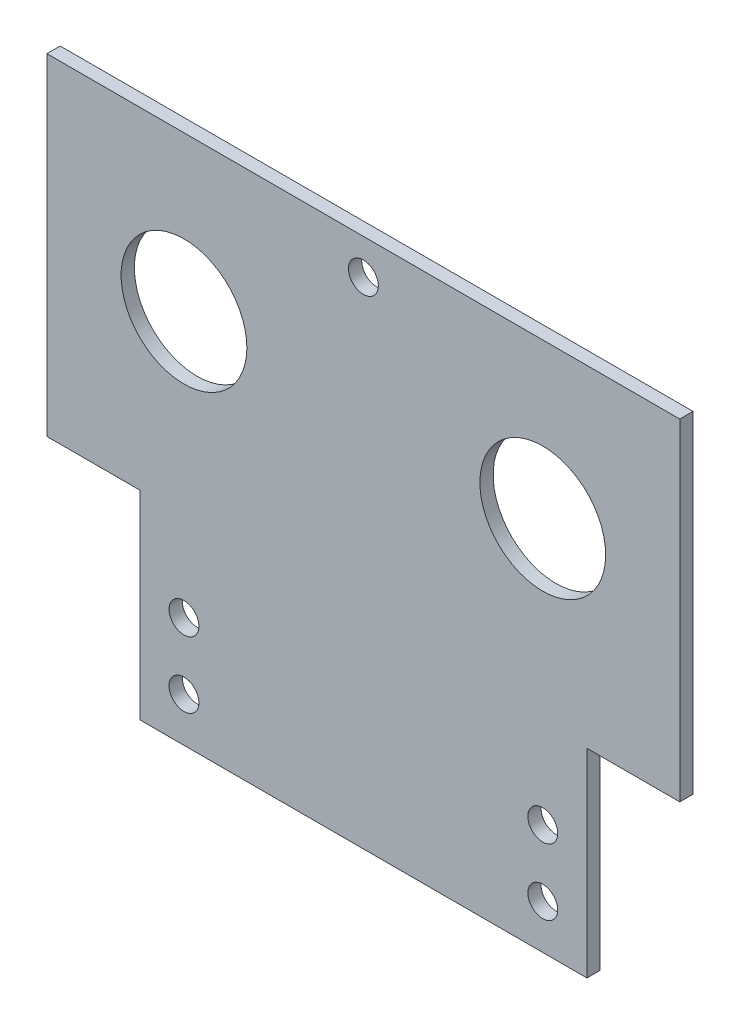
SolidWorks part; units mm, degrees
ref_plane "Front Plane" through (0, 0, 0) normal (0, 0, 1) x (1, 0, 0)
ref_plane "Top Plane" through (0, 0, 0) normal (0, 1, 0) x (1, 0, 0)
ref_plane "Right Plane" through (0, 0, 0) normal (1, 0, 0) x (0, 0, -1)
sketch "Sketch1" plane through (0, 0, 0) normal (0, 0, 1) x (1, 0, 0)
  line L1 (0, 0) -> (143.16, 0)
  line L2 (0, 0) -> (0, -120)
  line L3 (0, -120) -> (143.16, -120)
  line L4 (143.16, 0) -> (143.16, -120)
  dimension "D1" = 120
  dimension "D2" = 143.16
extrude "Boss-Extrude1" add sketch "Sketch1" along normal blind 3
sketch "Sketch2" plane through (0, 0, 3) normal (0, 0, 1) x (1, 0, 0)
  line L0 (0, 0) -> (0, -120) construction
  line L1 (143.16, -120) -> (143.16, 0) construction
  line L2 (0, -120) -> (143.16, -120) construction
  line L3 (143.16, 0) -> (0, 0) construction
  circle A0 centre (31, -35) radius 14.225
  circle A1 centre (112.16, -35) radius 14.225
  circle A3 centre (31, -110) radius 3.375
  circle A4 centre (112.16, -110) radius 3.375
  circle A7 centre (71.58, -8) radius 3.375
  circle A8 centre (31, -95) radius 3.375
  circle A9 centre (112.16, -95) radius 3.375
  point P10 (0, 0)
  point P11 (71.58, 0)
  dimension "D1" = 28.45
  dimension "D2" = 28.45
  dimension "D3" = 10
  dimension "D4" = 6.75
  dimension "D5" = 6.75
  dimension "D7" = 6.75
  dimension "D14" = 6.75
  dimension "D17" = 6.75
  dimension "D9" = 31
  dimension "D10" = 31
  dimension "D12" = 35
  dimension "D13" = 8
  dimension "D15" = 15
  dimension "D16" = 15
extrude "Cut-Extrude1" cut sketch "Sketch2" against normal through all
sketch "Sketch3" plane through (0, 0, 0) normal (0, 0, -1) x (-1, 0, 0)
  line L1 (0, -120) -> (-21, -120)
  line L2 (0, -120) -> (0, -75)
  line L3 (0, -75) -> (-21, -75)
  line L4 (-21, -120) -> (-21, -75)
  line L5 (-143.16, -120) -> (-122.16, -120)
  line L6 (-143.16, -120) -> (-143.16, -75)
  line L7 (-143.16, -75) -> (-122.16, -75)
  line L8 (-122.16, -120) -> (-122.16, -75)
  dimension "D1" = 21
  dimension "D2" = 45
  dimension "D3" = 21
  dimension "D4" = 45
extrude "Cut-Extrude2" cut sketch "Sketch3" against normal through all
